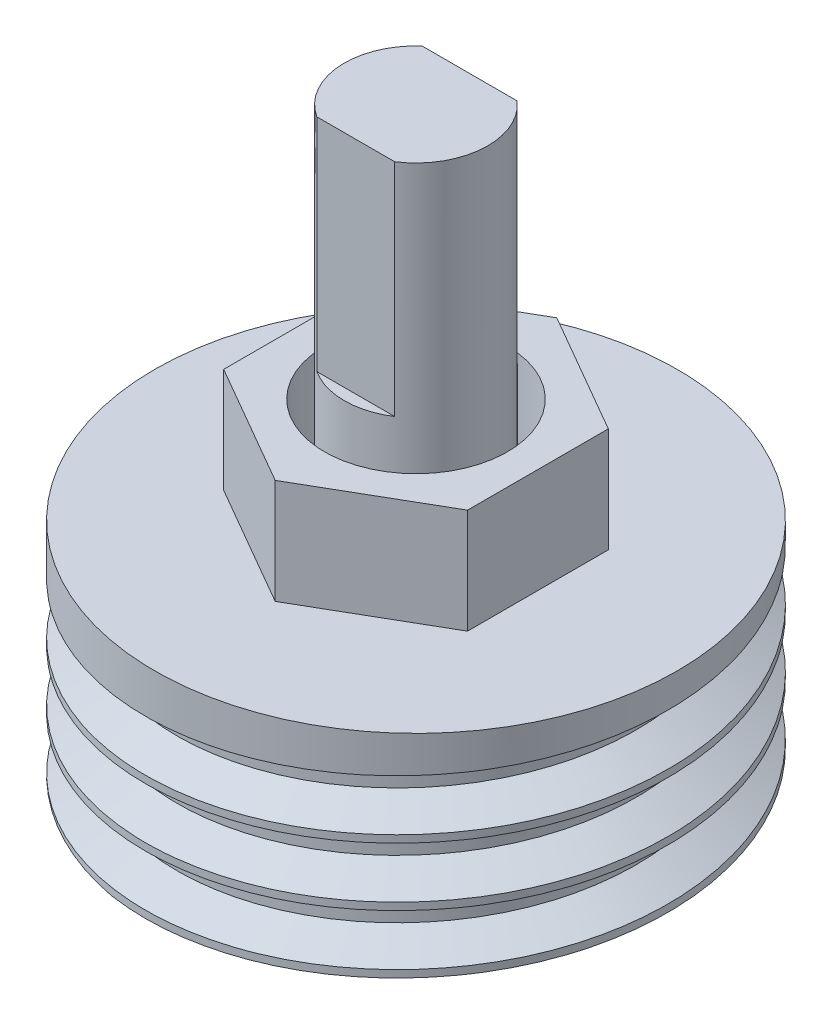
SolidWorks part; units mm, degrees
ref_plane "Front Plane" through (0, 0, 0) normal (0, 0, 1) x (1, 0, 0)
ref_plane "Top Plane" through (0, 0, 0) normal (0, 1, 0) x (1, 0, 0)
ref_plane "Right Plane" through (0, 0, 0) normal (1, 0, 0) x (0, 0, -1)
sketch "Sketch1" plane through (0, 0, 0) normal (0, 1, 0) x (1, 0, 0)
  line L0 (-1.725, 1.9453) -> (1.725, 1.9453)
  line L1 (-1.4097, -2.1847) -> (1.4097, -2.1847)
  arc A0 (-1.725, 1.9453) -> (-1.4097, -2.1847) centre (0, 0) ccw
  arc A1 (1.4097, -2.1847) -> (1.725, 1.9453) centre (0, 0) ccw
  dimension "D1" = 5.2
  dimension "D2" = 4.13
  dimension "D3" = 3.45
  dimension "D4" = 2.8194
extrude "Boss-Extrude1" add sketch "Sketch1" along normal blind 8
sketch "Sketch2" plane through (0, 0, 0) normal (0, -1, 0) x (1, 0, 0)
  circle A0 centre (0, 0) radius 2.6
  dimension "D1" = 5.2
extrude "Boss-Extrude2" add sketch "Sketch2" along normal blind 5.05
sketch "Sketch3" plane through (0, -5.05, 0) normal (0, -1, 0) x (1, 0, 0)
  circle A0 centre (0, 0) radius 9.47
  dimension "D1" = 18.94
extrude "Boss-Extrude3" add sketch "Sketch3" along normal blind 8 separate body
thread "Thread1" pitch 2.1167 method cut profile "Thread Profile1" start angle 0, offset 0, length 0, pitch 2.1167, diameter 18.94
ref_plane "Plane1" through (-9.47, -5.05, 0) normal (0, 0, 1) x (-1, 0, 0)
sketch "Thread Profile1" plane through (-9.47, -5.05, 0) normal (0, 0, 1) x (-1, 0, 0)
  line L0 (0, 0) -> (0, 2.1167) construction
  line L11 (0, 0) -> (0, 1.8521)
  line L12 (0, 1.8521) -> (-1.1457, 1.1906)
  line L13 (-1.1457, 1.1906) -> (-1.1457, 0.6615)
  line L15 (-1.1457, 0.6615) -> (0, 0)
  line L17 (-1.1457, 0.926) -> (0, 0.926) construction
  point P2 (0, 0)
  dimension "Pitch" = 2.1167
  dimension "Profile_Angle" = 60
  dimension "Profile_Land" = 0.5292
  dimension "Profile_Height" = 1.1457
sketch "Sketch8" plane through (0, -5.05, 0) normal (0, 1, 0) x (1, 0, 0)
  line L1 (0, 5.1038) -> (-4.42, 2.5519)
  line L2 (-4.42, 2.5519) -> (-4.42, -2.5519)
  line L3 (-4.42, -2.5519) -> (0, -5.1038)
  line L4 (0, -5.1038) -> (4.42, -2.5519)
  line L5 (4.42, -2.5519) -> (4.42, 2.5519)
  line L6 (4.42, 2.5519) -> (0, 5.1038)
  circle A0 centre (0, 0) radius 4.42 construction
  circle A1 centre (0, 0) radius 3.315
  dimension "D2" = 6.63
  dimension "D1" = 8.84
extrude "Boss-Extrude4" add sketch "Sketch8" along normal blind 3.8
